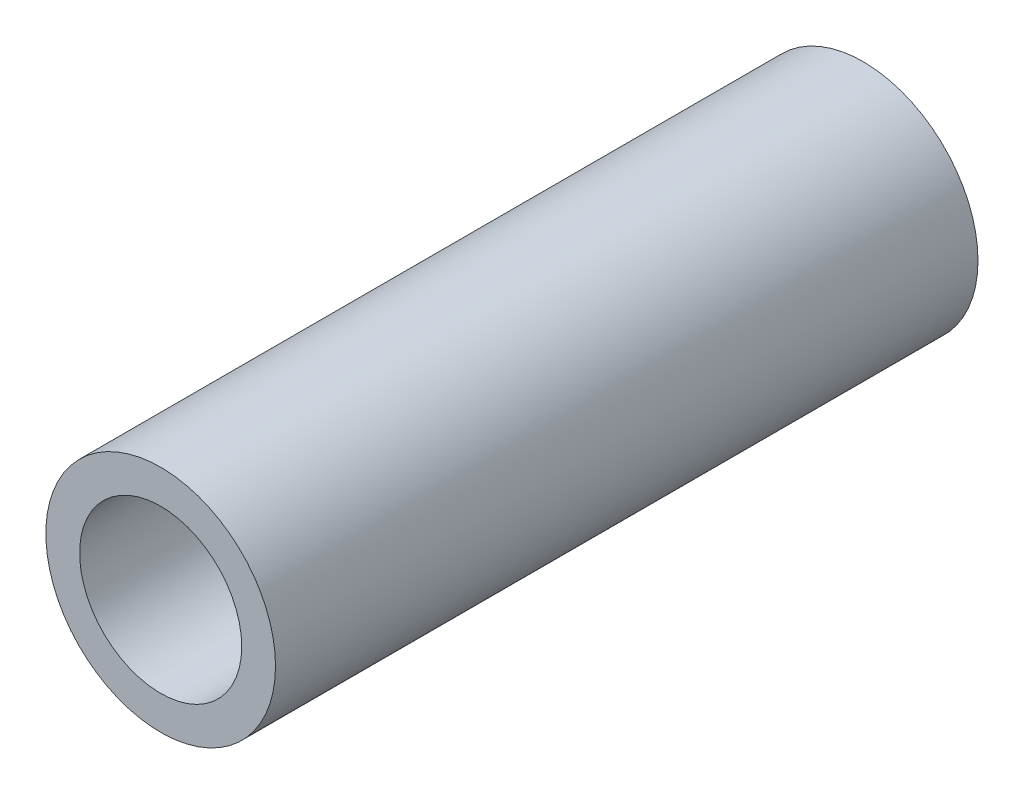
SolidWorks part; units mm, degrees
material "Silicon Rubber"
ref_plane "X-Y Datum" through (0, 0, 0) normal (0, 0, 1) x (1, 0, 0)
ref_plane "X-Z Datum" through (0, 0, 0) normal (0, 1, 0) x (1, 0, 0)
ref_plane "Y-Z Datum" through (0, 0, 0) normal (1, 0, 0) x (0, 0, -1)
sketch3d "3DSketch1"
  line L0 (0, 0, 0) -> (0, 0, 82.55)
  dimension "D1" = 82.55
sweep "Sweep1" add path "3DSketch1" circular profile diameter 26.9875 parameters "D3"=26.9875
sweep "Cut-Sweep1" cut path "3DSketch1<2>" circular profile diameter 19.05 parameters "D3"=19.05
sketch3d "3DSketch1<2>" same geometry as "3DSketch1"
